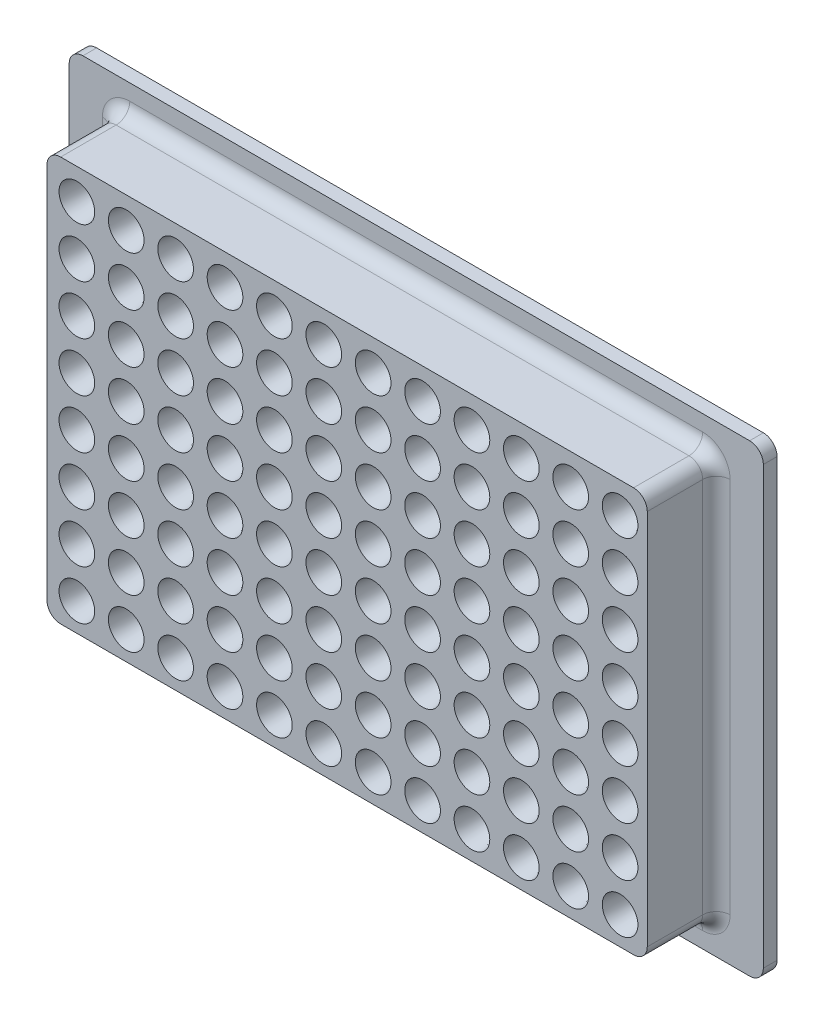
SolidWorks part; units mm, degrees
ref_plane "Front Plane" through (0, 0, 0) normal (0, 0, 1) x (1, 0, 0)
ref_plane "Top Plane" through (0, 0, 0) normal (0, 1, 0) x (1, 0, 0)
ref_plane "Right Plane" through (0, 0, 0) normal (1, 0, 0) x (0, 0, -1)
sketch "Sketch1" plane through (0, 0, 0) normal (0, 0, 1) x (1, 0, 0)
  line L1 (0, 0) -> (126.5, 0)
  line L2 (0, 0) -> (0, 84.5)
  line L3 (0, 84.5) -> (126.5, 84.5)
  line L4 (126.5, 0) -> (126.5, 84.5)
  dimension "D1" = 84.5
  dimension "D2" = 126.5
extrude "Boss-Extrude1" add sketch "Sketch1" along normal blind 2.5
sketch "Sketch3" plane through (0, 0, 2.5) normal (0, 0, 1) x (1, 0, 0)
  line L0 (0, 0) -> (126.5, 0) construction
  line L1 (8.55, 79.1) -> (117.95, 79.1)
  line L2 (8.55, 79.1) -> (8.55, 5.4)
  line L3 (8.55, 5.4) -> (117.95, 5.4)
  line L4 (117.95, 79.1) -> (117.95, 5.4)
  line L5 (0, 84.5) -> (0, 0) construction
  point P4 (63.25, 5.4)
  point P7 (63.25, 0)
  point P8 (8.55, 42.25)
  point P11 (0, 42.25)
  dimension "D1" = 73.7
  dimension "D2" = 109.4
extrude "Boss-Extrude2" add sketch "Sketch3" along normal blind 12.6
fillet "Fillet1" radius 2.5 12 edges at (126.5, 0, 1.25) (0, 0, 1.25) (126.5, 84.5, 1.25) (0, 84.5, 1.25) (63.25, 5.4, 2.5) (117.95, 42.25, 2.5) (8.55, 5.4, 8.8) (117.95, 5.4, 8.8) (117.95, 79.1, 8.8) (8.55, 79.1, 8.8) (63.25, 79.1, 2.5) (8.55, 42.25, 2.5)
sketch "Sketch2" plane through (0, 0, 15.1) normal (0, 0, 1) x (1, 0, 0)
  line L0 (0, 82) -> (0, 2.5) construction
  line L1 (124, 84.5) -> (2.5, 84.5) construction
  circle A0 centre (14, 73.5) radius 3.25
  dimension "D1" = 6.5
  dimension "D2" = 14
  dimension "D3" = 11
extrude "Cut-Extrude1" cut sketch "Sketch2" against normal blind 13 draft 8
pattern_linear "LPattern1" count 12 spacing 9 along (1, 0, 0) count 8 spacing 9 along (0, -1, 0) of "Cut-Extrude1"
